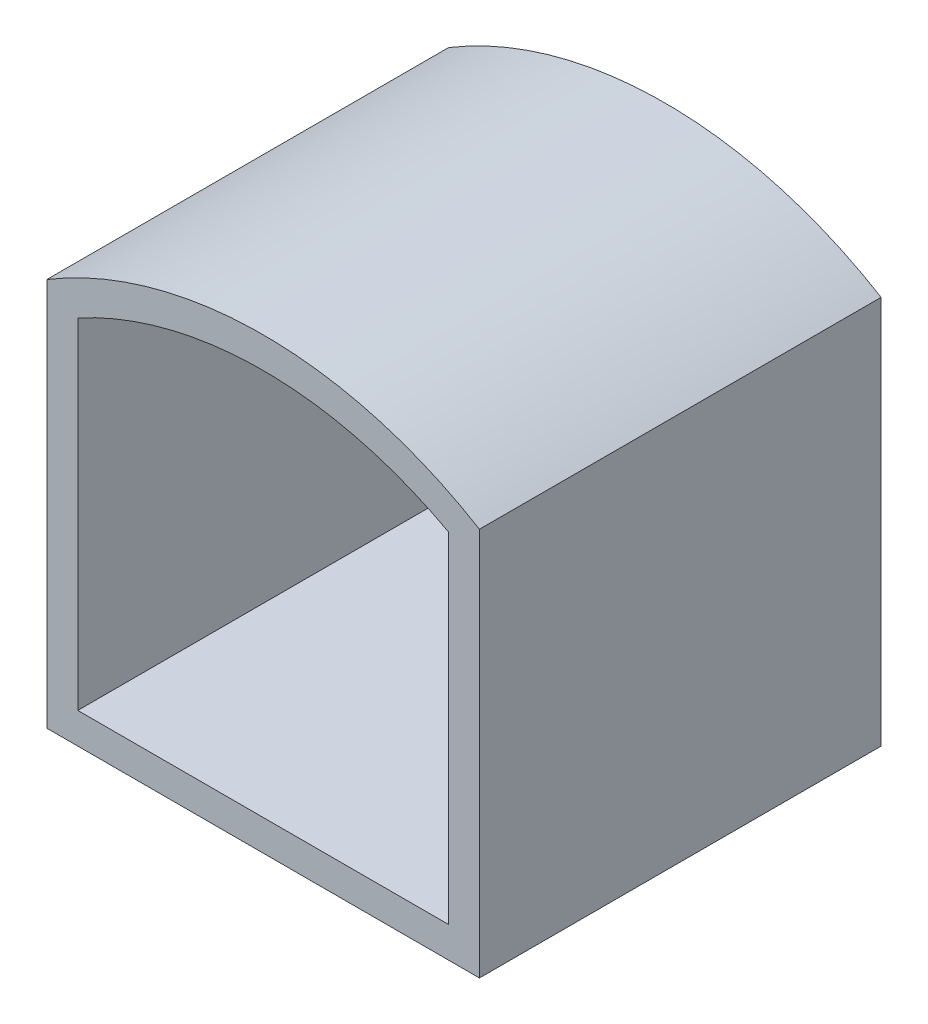
SolidWorks part; units mm, degrees
ref_plane "Front Plane" through (0, 0, 0) normal (0, 0, 1) x (1, 0, 0)
ref_plane "Top Plane" through (0, 0, 0) normal (0, 1, 0) x (1, 0, 0)
ref_plane "Right Plane" through (0, 0, 0) normal (1, 0, 0) x (0, 0, -1)
sketch "Sketch1" plane through (0, 0, 0) normal (0, 0, 1) x (1, 0, 0)
  line L5 (60, -55) -> (-60, -55)
  line L6 (60, -55) -> (60, 55)
  line L8 (-60, -55) -> (-60, 55)
  arc A0 (60, 55) -> (-60, 55) centre (0, -55) ccw
  point P5 (60, 0)
  dimension "D1" = 120
  dimension "D2" = 110
  dimension "D3" = 60
extrude "Boss-Extrude1" add sketch "Sketch1" along normal blind 120
shell "Shell1" thickness 10 removed face at (0, 3.8249, 120) outward yes
